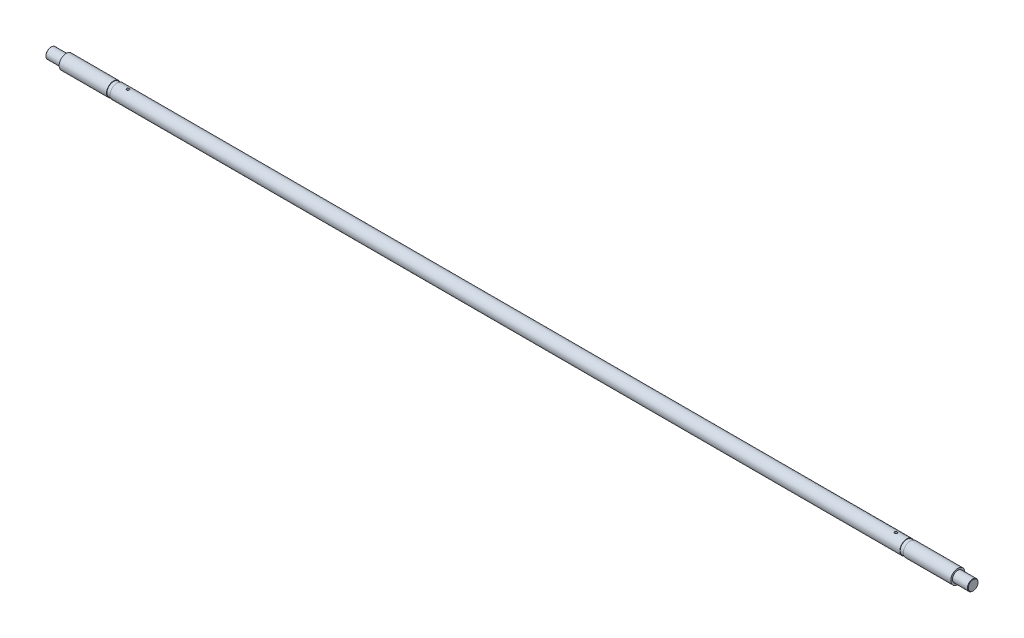
SolidWorks part; units mm, degrees
material "316L ST. STL."
ref_plane "Front" through (0, 0, 0) normal (0, 0, 1) x (1, 0, 0)
ref_plane "Top" through (0, 0, 0) normal (0, 1, 0) x (1, 0, 0)
ref_plane "Right" through (0, 0, 0) normal (1, 0, 0) x (0, 0, -1)
ref_axis "Axis1" through (0, 50, 0) along (0, -1, 0)
sketch "Sketch1" plane through (0, 0, 0) normal (1, 0, 0) x (0, 0, -1)
  circle A0 centre (0, 0) radius 12.7
  dimension "D1" = 25.4
extrude "Extrude1" add sketch "Sketch1" along normal mid plane 1601.5843
sketch "Sketch2" plane through (0, 0, 0) normal (1, 0, 0) x (0, 0, -1)
  circle A0 centre (0, 0) radius 9.5123
  dimension "D1" = 19.0246
extrude "Extrude2" add sketch "Sketch2" along normal mid plane 1656.588
sketch "Sketch3" plane through (0, 0, 0) normal (0, 0, 1) x (1, 0, 0)
  line L0 (800.7921, 12.7) -> (-800.7921, 12.7) construction
  line L1 (-715.5815, 12.7) -> (-709.2315, 12.7)
  line L2 (-715.5815, 12.7) -> (-715.5815, 11.9062)
  line L3 (-715.5815, 11.9062) -> (-709.2315, 11.9062)
  line L4 (-709.2315, 12.7) -> (-709.2315, 11.9062)
  line L5 (-828.294, 9.5123) -> (-828.294, -9.5123) construction
  line L6 (800.7921, 0) -> (-800.7921, 0) construction
  line L7 (709.2315, 12.7) -> (715.5815, 12.7)
  line L8 (709.2315, 12.7) -> (709.2315, 11.9062)
  line L9 (709.2315, 11.9062) -> (715.5815, 11.9062)
  line L10 (715.5815, 12.7) -> (715.5815, 11.9062)
  line L11 (828.294, -9.5123) -> (828.294, 9.5123) construction
  dimension "D1" = 6.35
  dimension "D2" = 112.7125
  dimension "D3" = 11.9062
  dimension "D4" = 6.35
  dimension "D5" = 11.9062
  dimension "D6" = 112.7125
revolve "Cut-Revolve1" cut sketch "Sketch3" angle 360 about axis through (800.7921, 0, 0) along (-1, 0, 0)
sketch "Sketch4" plane through (0, 0, 0) normal (0, 1, 0) x (1, 0, 0)
  line L0 (709.2315, 0) -> (-709.2315, 0) construction
  line L1 (709.2315, 0) -> (715.5815, 0) construction
  line L3 (0, 0) -> (0, 158.1872) construction
  circle A0 centre (-689.5973, 0) radius 2.3812
  circle A1 centre (689.5973, 0) radius 2.3812
  dimension "D1" = 4.7625
  dimension "D3" = 1379.1946
extrude "Extrude3" cut sketch "Sketch4" against normal mid plane 38.1
chamfer "Chamfer1" distance 0.762 angle 45 2 edges at (-828.294, 0, -9.5123) (828.294, 0, -9.5123)
ref_axis "Axis2" through (709.2315, 0, 0) along (-1, 0, 0)
